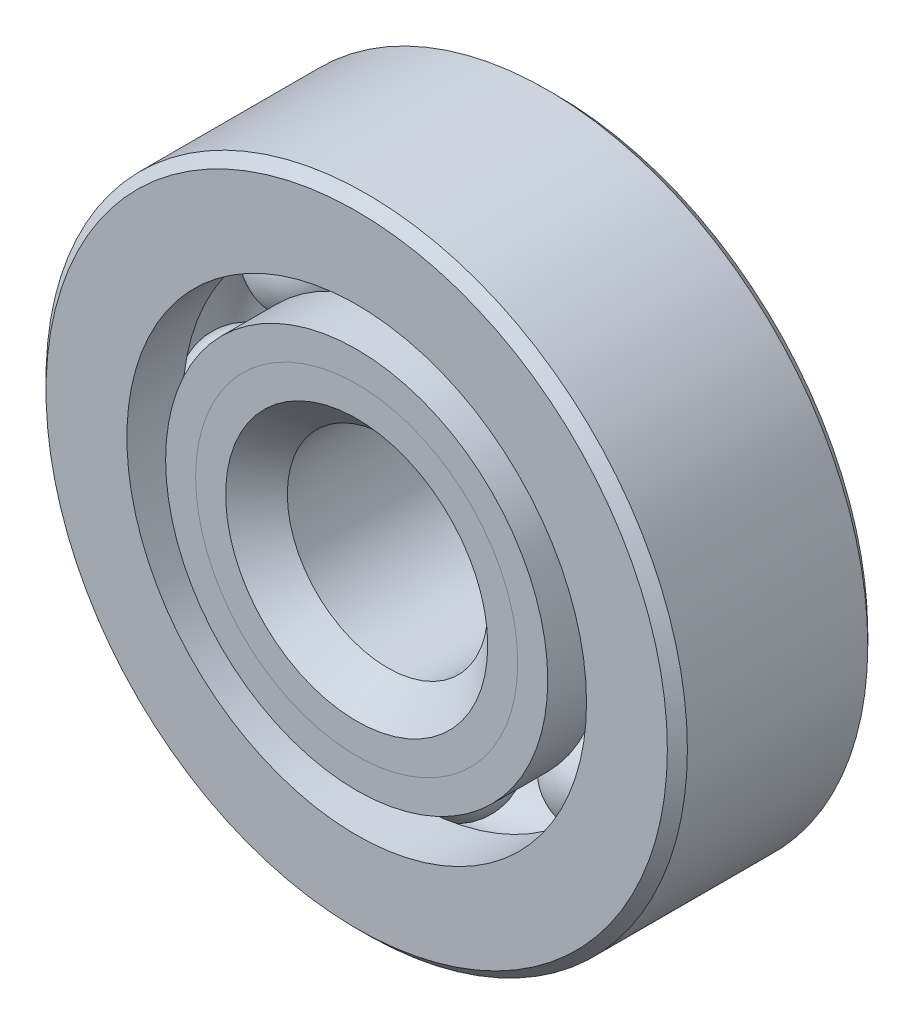
SolidWorks part; units mm, degrees
ref_plane "Front Plane" through (0, 0, 0) normal (0, 0, 1) x (1, 0, 0)
ref_plane "Top Plane" through (0, 0, 0) normal (0, 1, 0) x (1, 0, 0)
ref_plane "Right Plane" through (0, 0, 0) normal (1, 0, 0) x (0, 0, -1)
sketch "Sketch1" plane through (0, 0, 0) normal (1, 0, 0) x (0, 0, -1)
  line L0 (-2.5, 0) -> (2.5, 0) construction
  line L1 (0, 8) -> (0, -8) construction
  line L2 (2.25, 8) -> (-2.25, 8)
  line L3 (-2.25, 8) -> (-2.5, 7.75)
  line L4 (-2.5, 7.75) -> (-2.5, 5.7335)
  line L5 (-2.5, 5.7335) -> (-1.1111, 5.7335)
  line L6 (2.5, 5.7335) -> (1.1111, 5.7335)
  line L7 (2.5, 7.75) -> (2.5, 5.7335)
  line L8 (2.25, 8) -> (2.5, 7.75)
  line L9 (0, 8) -> (0, 5.25) construction
  line L10 (0, 5.25) -> (0, 2.5) construction
  line L11 (-2.5, -8) -> (2.5, -8) construction
  line L12 (0, -2.5) -> (0, 2.5) construction
  line L13 (2.5, -2.5) -> (2.5, 2.5) construction
  arc A0 (-1.1111, 5.7335) -> (1.1111, 5.7335) centre (0, 5.25) cw
  point P14 (0, 2.5)
  point P15 (0, -2.5)
  point P19 (0, -8)
  point P23 (0, 0)
  point P25 (2.5, 0)
  dimension "OD" = 16
  dimension "D1" = 45
  dimension "D2" = 0.25
  dimension "D3" = 2.2222
  dimension "D4" = 0.4835
  dimension "Width" = 5
  dimension "Shaft Dia" = 5
revolve "Revolve1" add sketch "Sketch1" angle 360 about L0
sketch "Sketch2" plane through (0, 0, 0) normal (1, 0, 0) x (0, 0, -1)
  line L0 (-2.5, 4.7665) -> (-1.1111, 4.7665)
  line L1 (-2.5, 7.75) -> (-2.5, -7.75) construction
  line L2 (-2.5, 4.7665) -> (-2.5, 4.0178)
  line L3 (-2.5, 4.0178) -> (-1.7513, 3.2691)
  line L4 (-1.7513, 3.2691) -> (0, 3.2691)
  line L5 (0, 8) -> (0, -8) construction
  line L6 (0, 3.2691) -> (0, 4.0382)
  line L7 (0, 4.0382) -> (0, 2.5) construction
  line L8 (-2.5, 4.7665) -> (-2.5, 3.2691) construction
  line L9 (-2.5, 3.2691) -> (-1.7513, 3.2691) construction
  arc A0 (-1.1111, 4.7665) -> (0, 4.0382) centre (0, 5.25) ccw
  arc A1 (1.1111, 5.7335) -> (-1.1111, 5.7335) centre (0, 5.25) ccw construction
  circle A2 centre (0, 5.25) radius 1.2118 construction
  dimension "D1" = 45
revolve "Revolve2" add sketch "Sketch2" angle 360 about L0
sketch "Sketch3" plane through (0, 0, 0) normal (1, 0, 0) x (0, 0, -1)
  line L0 (-2.5, 4.0178) -> (-1.7513, 3.2691)
  line L1 (-1.7513, 3.2691) -> (0, 3.2691)
  line L2 (0, 3.2691) -> (0, 4.0382)
  line L3 (-2.5, 4.0178) -> (-2.5, 3.2691)
  line L4 (-2.5, 4.7665) -> (-2.5, 3.2691) construction
  line L5 (-2.5, 3.2691) -> (-1.7309, 2.5)
  line L6 (-1.7309, 2.5) -> (2.25, 2.5)
  line L7 (2.25, 8) -> (2.25, -8) construction
  line L8 (2.25, 2.5) -> (2.5, 2.75)
  line L9 (2.5, -7.75) -> (2.5, 7.75) construction
  line L10 (2.5, 2.75) -> (2.5, 4.7665)
  line L11 (2.5, 4.7665) -> (1.1111, 4.7665)
  line L13 (2.25, 8) -> (2.5, 7.75) construction
  circle A0 centre (0, 5.25) radius 1.2118 construction
  arc A1 (1.1111, 4.7665) -> (0, 4.0382) centre (0, 5.25) cw
revolve "Revolve3" add sketch "Sketch3" angle 360 about L0
sketch "Sketch4" plane through (0, 0, 0) normal (1, 0, 0) x (0, 0, -1)
  line L0 (-1.2118, 5.25) -> (1.2118, 5.25)
  circle A1 centre (0, 5.25) radius 1.2118 construction
  arc A2 (-1.2118, 5.25) -> (1.2118, 5.25) centre (0, 5.25) cw
  arc A3 (1.1111, 5.7335) -> (-1.1111, 5.7335) centre (0, 5.25) ccw construction
revolve "Revolve4" add sketch "Sketch4" angle 360 about L0
ref_axis "Axis1" through (0, 0, -2.5) along (0, 0, 1)
pattern_circular "CirPattern1" count 8 every 45 about axis through (0, 0, -2.5) along (0, 0, 1) of bodies 104
sketch "REF" plane through (0, 0, 0) normal (1, 0, 0) x (0, 0, -1)
  line L0 (2.25, 2.5) -> (2.5, 2.75) construction
  line L1 (-1.7309, 2.5) -> (2.25, 2.5) construction
  line L2 (-2.5, 3.2691) -> (-1.7309, 2.5) construction
  line L3 (2.25, 2.5) -> (2.5, 2.75) construction
  line L4 (-1.7309, 2.5) -> (2.25, 2.5) construction
  line L5 (-2.5, 3.2691) -> (-1.7309, 2.5) construction
  line L6 (-2.5, 0) -> (2.5, 0) construction
  line L7 (-2.5, 0) -> (2.5, 0) construction
  line L8 (2.25, -2.5) -> (2.5, -2.75) construction
  line L9 (-1.7309, -2.5) -> (2.25, -2.5) construction
  line L10 (-2.5, -3.2691) -> (-1.7309, -2.5) construction
ref_axis "Center Axis 1" through (0, 0, -2.25) along (0, 0, 1)
equation "\"D2@Sketch1\" = \"Width@Sketch1\"*.05"
equation "\"D3@Sketch1\" = \"Width@Sketch1\"/2.25"
equation "\"D4@Sketch1\" = (((\"OD@Sketch1\"-\"Width@Sketch1\")/2)/3.25)/3.5"
equation "\"D2@CirPattern1\" = 360/\"Balls@CirPattern1\""
